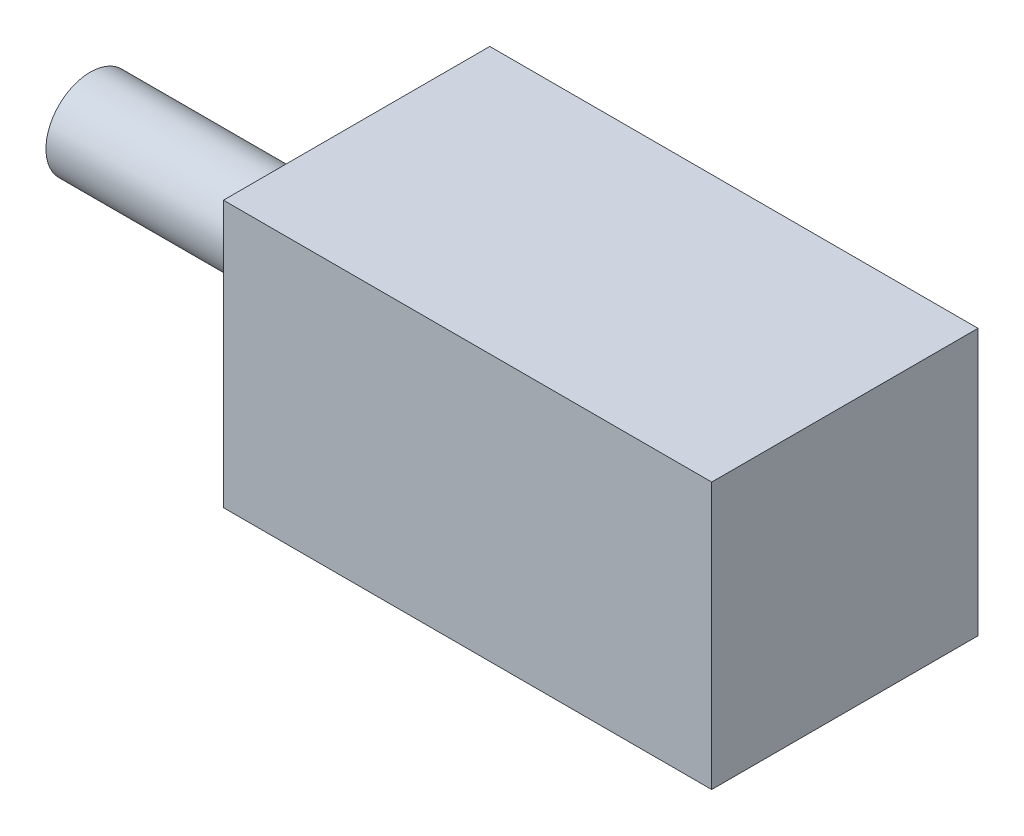
SolidWorks part; units mm, degrees
ref_plane "Front Plane" through (0, 0, 0) normal (0, 0, 1) x (1, 0, 0)
ref_plane "Top Plane" through (0, 0, 0) normal (0, 1, 0) x (1, 0, 0)
ref_plane "Right Plane" through (0, 0, 0) normal (1, 0, 0) x (0, 0, -1)
sketch "Sketch1" plane through (0, 0, 0) normal (0, 1, 0) x (1, 0, 0)
  line L1 (0, -19.05) -> (69.85, -19.05)
  line L2 (0, -19.05) -> (0, 19.05)
  line L3 (0, 19.05) -> (69.85, 19.05)
  line L4 (69.85, -19.05) -> (69.85, 19.05)
  dimension "D1" = 38.1
  dimension "D2" = 19.05
  dimension "D3" = 69.85
  dimension "D4" = 0
extrude "Boss-Extrude1" add sketch "Sketch1" along normal blind 19.05 and the other way blind 19.05
sketch "Sketch3" plane through (0, 0, 0) normal (0, 1, 0) x (1, 0, 0)
  line L0 (0, 0) -> (-52.9167, 0) construction
  line L2 (0, 0) -> (-38.1, 0)
  line L3 (0, 0) -> (0, 6.35)
  line L4 (0, 6.35) -> (-38.1, 6.35)
  line L5 (-38.1, 0) -> (-38.1, 6.35)
  dimension "D1" = 6.35
  dimension "D2" = 38.1
revolve "Revolve1" add sketch "Sketch3" angle 360 about L0
